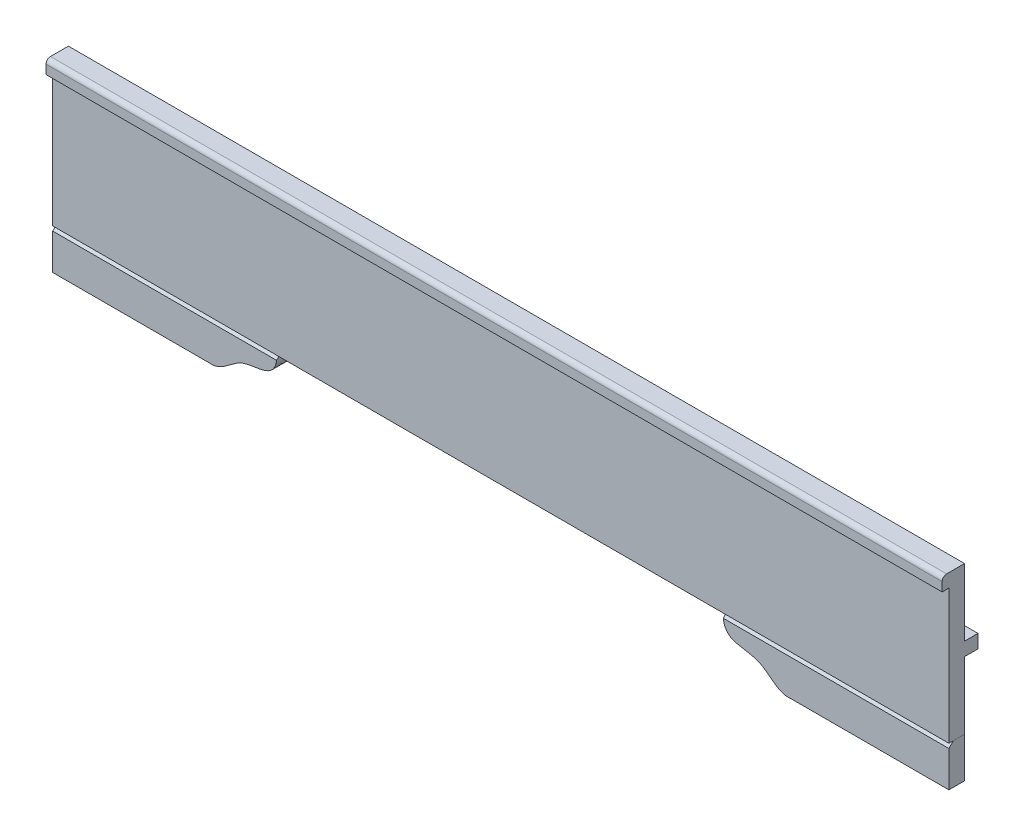
SolidWorks part; units mm, degrees
material "Mahogany"
ref_plane "Front Plane" through (0, 0, 0) normal (0, 0, 1) x (1, 0, 0)
ref_plane "Top Plane" through (0, 0, 0) normal (0, 1, 0) x (1, 0, 0)
ref_plane "Right Plane" through (0, 0, 0) normal (1, 0, 0) x (0, 0, -1)
sketch "Sketch1" plane through (0, 0, 0) normal (0, 0, 1) x (1, 0, 0)
  line L1 (0, 0) -> (-2000, 0)
  line L2 (0, 0) -> (0, -30)
  line L3 (0, -30) -> (-2000, -30)
  line L4 (-2000, 0) -> (-2000, -30)
  dimension "D1" = 30
  dimension "D2" = 2000
extrude "Boss-Extrude1" add sketch "Sketch1" along normal blind 50
sketch "Sketch2" plane through (0, 0, 0) normal (0, 0, -1) x (-1, 0, 0)
  line L1 (0, -30) -> (2000, -30)
  line L2 (0, -30) -> (0, -330)
  line L3 (0, -330) -> (2000, -330)
  line L4 (2000, -30) -> (2000, -330)
  dimension "D1" = 2000
  dimension "D2" = 300
extrude "Boss-Extrude2" add sketch "Sketch2" against normal blind 35
fillet "Fillet1" radius 10 1 edges at (-1000, 0, 50)
sketch "Sketch3" plane through (0, 0, 35) normal (0, 0, 1) x (1, 0, 0)
  line L0 (-503.9665, -330) -> (0, -330)
  line L1 (-2000, -330) -> (-1500, -330)
  line L2 (-2000, -330) -> (-2000, -420)
  line L3 (-2000, -420) -> (-1650, -420)
  line L4 (0, -330) -> (0, -420)
  line L5 (-353.9665, -420) -> (0, -420)
  spline S0 degree 3 poles (-1500, -330) (-1499.6197, -385.5425) (-1581.343, -359.1134) (-1622.5245, -423.2318) (-1650, -420) knots 0 0 0 0 0.573312 1 1 1 1
  spline S2 degree 3 poles (-503.9665, -330) (-504.4145, -385.6302) (-422.3443, -358.815) (-381.6573, -423.6992) (-353.9665, -420) knots 0 0 0 0 0.572853 1 1 1 1
  dimension "D1" = 500
  dimension "D2" = 90
  dimension "D3" = 350
  dimension "D4" = 55
  dimension "D5" = 60
  dimension "D6" = 70
  dimension "D7" = 35
  dimension "D8" = 20
  dimension "D9" = 40
  dimension "D10" = 40
  dimension "D11" = 90
  dimension "D12" = 35
  dimension "D13" = 20
  dimension "D14" = 60
  dimension "D15" = 70
  dimension "D16" = 80
  dimension "D17" = 90
extrude "Boss-Extrude3" add sketch "Sketch3" against normal blind 35 separate body
chamfer "Chamfer1" distance 10 angle 45 1 edges at (-1750, -330, 35)
chamfer "Chamfer2" distance 10 angle 45 1 edges at (-251.9832, -330, 35)
sketch "Sketch6" plane through (0, 0, 0) normal (0, 0, -1) x (-1, 0, 0)
  line L0 (0, -330) -> (0, 0) construction
  line L1 (0, -150) -> (2000, -150)
  line L2 (0, -150) -> (0, -180)
  line L3 (0, -180) -> (2000, -180)
  line L4 (2000, -150) -> (2000, -180)
  line L5 (2000, 0) -> (2000, -330) construction
  line L6 (0, 0) -> (2000, 0) construction
  dimension "D1" = 150
  dimension "D2" = 30
extrude "Boss-Extrude4" add sketch "Sketch6" along normal blind 30
